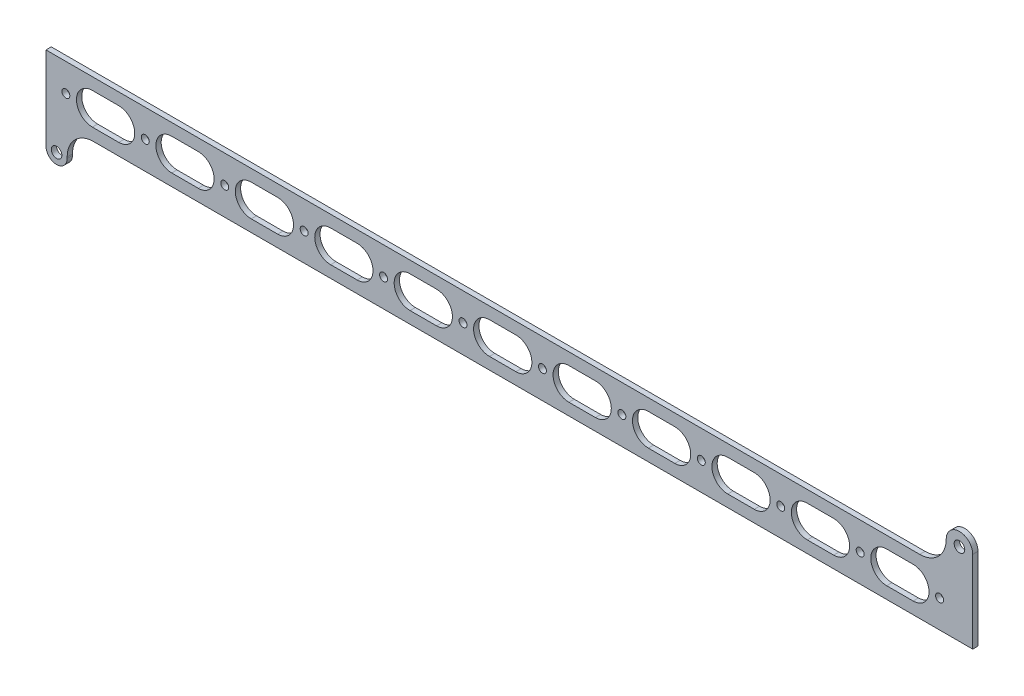
SolidWorks part; units mm, degrees
material "Thornel Mat VMA"
ref_plane "前视基准面" through (0, 0, 0) normal (0, 0, 1) x (1, 0, 0)
ref_plane "上视基准面" through (0, 0, 0) normal (0, 1, 0) x (1, 0, 0)
ref_plane "右视基准面" through (0, 0, 0) normal (1, 0, 0) x (0, 0, -1)
sketch "草图1" plane through (0, 0, 0) normal (0, 0, 1) x (1, 0, 0)
  line L1 (-175, -10.5) -> (175, -10.5)
  line L2 (-175, -10.5) -> (-175, 10.5)
  line L3 (-175, 10.5) -> (175, 10.5)
  line L4 (175, -10.5) -> (175, 10.5)
  line L5 (-175, -10.5) -> (175, 10.5) construction
  line L6 (-175, 10.5) -> (175, -10.5) construction
  point P0 (0, 0)
  dimension "D1" = 21
  dimension "D2" = 350
extrude "凸台-拉伸1" add sketch "草图1" along normal blind 2
sketch "草图2" plane through (0, 0, 2) normal (0, 0, 1) x (1, 0, 0)
  line L0 (-175, -10.5) -> (175, -10.5) construction
  line L1 (-175, -21) -> (-175, -10.5)
  line L2 (-167, -21) -> (-167, -10.5)
  line L3 (-167, -10.5) -> (-175, -10.5)
  line L4 (175, 20.5) -> (175, 10.5)
  line L5 (175, 10.5) -> (-175, 10.5) construction
  line L6 (165, 20.5) -> (165, 10.5)
  line L7 (165, 10.5) -> (175, 10.5)
  circle A0 centre (-171, -21) radius 2
  arc A1 (-175, -21) -> (-167, -21) centre (-171, -21) ccw
  circle A2 centre (170, 20.5) radius 2
  arc A3 (175, 20.5) -> (165, 20.5) centre (170, 20.5) ccw
  dimension "D1" = 4
  dimension "D3" = 2
  dimension "D4" = 4
  dimension "D5" = 3
  dimension "D2" = 10.5
  dimension "D6" = 10
extrude "凸台-拉伸2" add sketch "草图2" against normal up to surface (2 mm away) up to face at (0, 0, 0)
fillet "圆角1" radius 10 2 edges at (-167, -10.5, 1) (165, 10.5, 1)
sketch "草图3" plane through (0, 0, 2) normal (0, 0, 1) x (1, 0, 0)
  circle A0 centre (-137.5, 0) radius 1.75 construction
  circle A1 centre (-137.5, 0) radius 1.75 construction
  circle A2 centre (-137.5, 0) radius 1.5
  dimension "D1" = 3
extrude "切除-拉伸1" cut sketch "草图3" against normal mid plane 60
pattern_linear "阵列(线性)1" count 10 spacing 30 along (1, 0, 0) of "切除-拉伸1"
sketch "草图4" plane through (0, 0, 2) normal (0, 0, 1) x (1, 0, 0)
  line L0 (-137.5, 0) -> (-167.5, 0) construction
  line L1 (132.5, 0) -> (162.5, 0) construction
  circle A1 centre (-167.5, 0) radius 1.5
  circle A2 centre (162.5, 0) radius 1.5
  circle A3 centre (-137.5, 0) radius 1.5 construction
  dimension "D1" = 30
  dimension "D2" = 30
extrude "切除-拉伸2" cut sketch "草图4" against normal blind 10
sketch "草图5" plane through (0, 0, 2) normal (0, 0, 1) x (1, 0, 0)
  line L0 (-157.5, 0) -> (-147.5, 0) construction
  line L1 (-157.5, 6) -> (-147.5, 6)
  line L2 (-157.5, -6) -> (-147.5, -6)
  line L3 (-147.5, 0) -> (0, 0) construction
  arc A0 (-157.5, 6) -> (-157.5, -6) centre (-157.5, 0) ccw
  arc A1 (-147.5, -6) -> (-147.5, 6) centre (-147.5, 0) ccw
  circle A5 centre (-137.5, 0) radius 1.5 construction
  circle A6 centre (-167.5, 0) radius 1.5 construction
  point P3 (-152.5, 0)
  dimension "D3" = 6
  dimension "D1" = 2.5
  dimension "D2" = 2.5
extrude "切除-拉伸3" cut sketch "草图5" against normal blind 5
pattern_linear "阵列(线性)2" count 11 spacing 30 along (1, 0, 0) of "切除-拉伸3"
